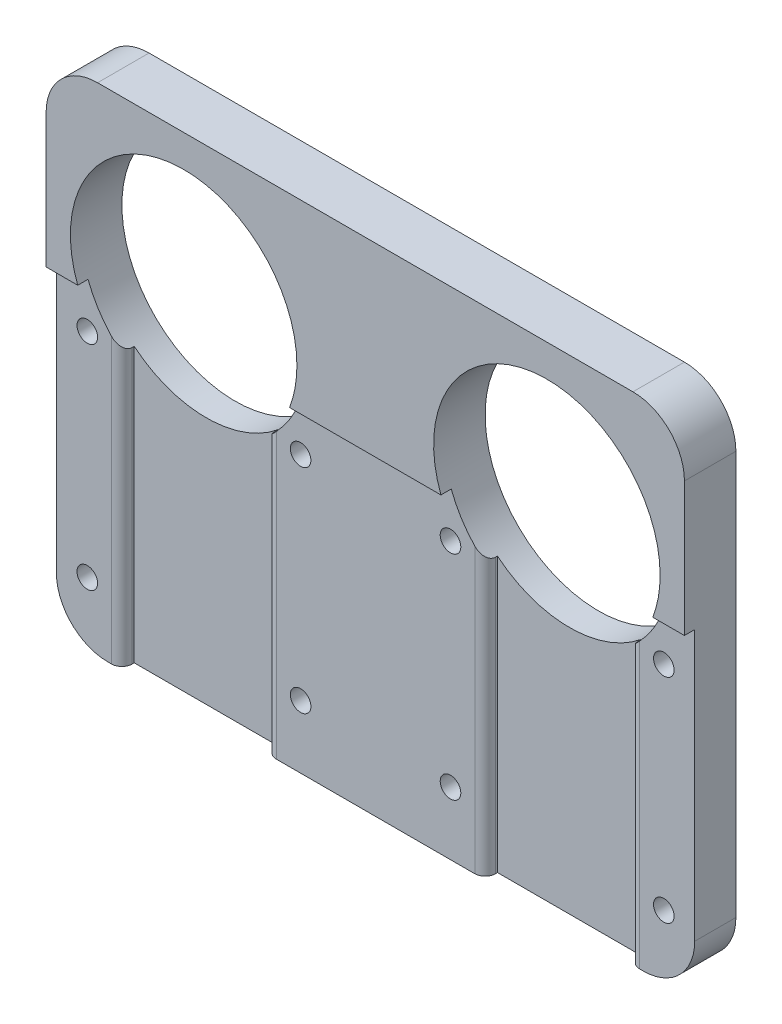
SolidWorks part; units mm, degrees
ref_plane "前视基准面" through (0, 0, 0) normal (0, 0, 1) x (1, 0, 0)
ref_plane "上视基准面" through (0, 0, 0) normal (0, 1, 0) x (1, 0, 0)
ref_plane "右视基准面" through (0, 0, 0) normal (1, 0, 0) x (0, 0, -1)
sketch "草图1" plane through (0, 0, 0) normal (0, 0, 1) x (1, 0, 0)
  line L1 (-5.8171, 42.0726) -> (56.1829, 42.0726)
  line L2 (-5.8171, 42.0726) -> (-5.8171, -3.1474)
  line L3 (-5.8171, -3.1474) -> (56.1829, -3.1474)
  line L4 (56.1829, 42.0726) -> (56.1829, -3.1474)
  dimension "D1" = 45.22
  dimension "D2" = 62
extrude "凸台-拉伸1" add sketch "草图1" along normal blind 4
sketch "草图7" plane through (0, 42.0726, 0) normal (0, 1, 0) x (1, 0, 0)
  line L4 (-5.8171, 0) -> (-5.8171, -4)
  line L5 (56.1829, 0) -> (-5.8171, 0)
  line L6 (-5.8171, 0) -> (-5.8171, -4)
  line L7 (-5.8171, -4) -> (56.1829, -4)
  line L9 (56.1829, 0) -> (-5.8171, 0)
  line L11 (-5.8171, -4) -> (56.1829, -4)
  line L12 (56.1829, -4) -> (56.1829, 0)
  line L13 (56.1829, -4) -> (56.1829, 0)
  dimension "D1" = 0
extrude "凸台-拉伸4" add sketch "草图7" along normal blind 4
sketch "草图2" plane through (0, 0, 4) normal (0, 0, 1) x (1, 0, 0)
  line L0 (-5.8171, 46.0726) -> (-5.8171, -3.1474) construction
  line L1 (-5.8171, -3.1474) -> (56.1829, -3.1474) construction
  line L3 (56.1829, -3.1474) -> (56.1829, 46.0726) construction
  line L5 (0.5429, -3.1474) -> (14.5429, -3.1474)
  line L6 (0.5429, -3.1474) -> (0.5429, 24.8526)
  line L7 (0.5429, 24.8526) -> (14.5429, 24.8526)
  line L8 (14.5429, -3.1474) -> (14.5429, 24.8526)
  line L9 (49.8229, -3.1474) -> (35.8229, -3.1474)
  line L10 (49.8229, -3.1474) -> (49.8229, 24.8526)
  line L11 (49.8229, 24.8526) -> (35.8229, 24.8526)
  line L12 (35.8229, -3.1474) -> (35.8229, 24.8526)
  line L13 (-5.8171, 46.0726) -> (56.1829, 46.0726) construction
  circle A0 centre (-2.8171, 2.9626) radius 1
  circle A1 centre (17.9029, 2.9626) radius 1
  circle A2 centre (-2.8171, 23.6626) radius 1
  circle A3 centre (17.9029, 23.6626) radius 1
  circle A4 centre (7.5429, 31.9626) radius 11
  circle A5 centre (53.1829, 2.9626) radius 1
  circle A6 centre (32.4629, 2.9626) radius 1
  circle A7 centre (32.4629, 23.6626) radius 1
  circle A8 centre (53.1829, 23.6626) radius 1
  circle A9 centre (42.8229, 31.9626) radius 11
  line M9 (-5.8171, -3.1474) -> (56.1829, -3.1474)
  dimension "D1" = 2
  dimension "D2" = 2
  dimension "D3" = 2
  dimension "D4" = 2
  dimension "D5" = 2
  dimension "D6" = 2
  dimension "D7" = 2
  dimension "D8" = 2
  dimension "D9" = 22
  dimension "D10" = 22
  dimension "D11" = 3
  dimension "D12" = 3
  dimension "D13" = 6.11
  dimension "D14" = 6.11
  dimension "D15" = 20.7
  dimension "D17" = 20.7
  dimension "D18" = 20.72
  dimension "D21" = 6.11
  dimension "D22" = 6.11
  dimension "D23" = 3
  dimension "D24" = 20.72
  dimension "D25" = 20.7
  dimension "D26" = 3
  dimension "D27" = 14.11
  dimension "D30" = 20.7
  dimension "D16" = 20.72
  dimension "D19" = 14.11
  dimension "D20" = 13.36
  dimension "D28" = 13.36
  dimension "D29" = 20.72
  dimension "D31" = 28
  dimension "D32" = 14
  dimension "D33" = 6.36
  dimension "D34" = 28
  dimension "D35" = 14
  dimension "D36" = 6.36
extrude "切除-拉伸1" cut sketch "草图2" against normal blind 4 contours L8 A4 L6 L7 | L10 A9 L12 L11 | L6 A4 L8 L7 | L12 A9 L10 L11 | A2 | A3 | A0 | A1 | A7 | A8 | A5 | A6 region at (7.5429, 33.0873, 4) region at (7.5429, 23.2183, 4) region at (42.8229, 23.2183, 4) region at (42.8229, 33.0873, 4)
sketch "草图3" plane through (0, 0, 0) normal (0, 0, -1) x (-1, 0, 0)
  circle A0 centre (-53.1829, 2.9626) radius 2
  circle A1 centre (-32.4629, 2.9626) radius 2
  circle A2 centre (-17.9029, 2.9626) radius 2
  circle A3 centre (2.8171, 2.9626) radius 2
  circle A4 centre (-53.1829, 23.6626) radius 2
  circle A5 centre (-32.4629, 23.6626) radius 2
  circle A6 centre (-17.9029, 23.6626) radius 2
  circle A7 centre (2.8171, 23.6626) radius 2
  dimension "D1" = 4
  dimension "D2" = 4
  dimension "D3" = 4
  dimension "D4" = 4
  dimension "D5" = 4
  dimension "D6" = 4
  dimension "D7" = 4
  dimension "D8" = 4
extrude "切除-拉伸2" cut sketch "草图2<3>" against normal blind 1.2 contours A4 L6 L8 M9 | A9 L12 L10 M9 region at (7.5429, 9.3163, 4) region at (42.8229, 9.3163, 4)
sketch "草图2<3>" plane through (0, 0, 4) normal (0, 0, 1) x (1, 0, 0) same geometry as "草图2"
fillet "圆角2" radius 5 1 edges at (-5.8171, -3.1474, 2)
fillet "圆角4" radius 5 1 edges at (56.1829, -3.1474, 2)
fillet "圆角6" radius 1 1 edges at (14.5429, 10.165, 4)
fillet "圆角7" radius 1 1 edges at (0.5429, 10.165, 4)
fillet "圆角8" radius 1 1 edges at (35.8229, 10.165, 4)
fillet "圆角9" radius 1 1 edges at (49.8229, 10.165, 4)
extrude "切除-拉伸6" cut sketch "草图3" against normal blind 1.5
fillet "圆角10" radius 5 1 edges at (56.1829, 46.0726, 2)
fillet "圆角11" radius 5 1 edges at (-5.8171, 46.0726, 2)
sketch "草图8" plane through (0, 0, 4) normal (0, 0, 1) x (1, 0, 0)
  line L0 (56.1829, 28.0726) -> (-5.8171, 28.0726)
  line L10 (51.1829, 46.0726) -> (-0.8171, 46.0726)
  line L11 (-5.8171, 41.0726) -> (-5.8171, 1.8526)
  line L12 (-0.8171, -3.1474) -> (-0.4571, -3.1474)
  line L13 (-0.4571, -3.1474) -> (-0.4571, 24.4128)
  line L14 (15.5429, 24.4128) -> (15.5429, -3.1474)
  line L15 (15.5429, -3.1474) -> (34.8229, -3.1474)
  line L16 (34.8229, -3.1474) -> (34.8229, 24.4128)
  line L17 (50.8229, 24.4128) -> (50.8229, -3.1474)
  line L18 (50.8229, -3.1474) -> (51.1829, -3.1474)
  line L19 (56.1829, 1.8526) -> (56.1829, 41.0726)
  line L20 (51.1829, 46.0726) -> (-0.8171, 46.0726)
  line L21 (-5.8171, 41.0726) -> (-5.8171, 1.8526)
  line L22 (-0.8171, -3.1474) -> (-0.4571, -3.1474)
  line L23 (-0.4571, -3.1474) -> (-0.4571, 24.4128)
  line L24 (15.5429, 24.4128) -> (15.5429, -3.1474)
  line L25 (15.5429, -3.1474) -> (34.8229, -3.1474)
  line L26 (34.8229, -3.1474) -> (34.8229, 24.4128)
  line L27 (50.8229, 24.4128) -> (50.8229, -3.1474)
  line L28 (50.8229, -3.1474) -> (51.1829, -3.1474)
  line L29 (56.1829, 1.8526) -> (56.1829, 41.0726)
  arc A6 (-0.8171, 46.0726) -> (-5.8171, 41.0726) centre (-0.8171, 41.0726) ccw
  arc A7 (-5.8171, 1.8526) -> (-0.8171, -3.1474) centre (-0.8171, 1.8526) ccw
  arc A8 (15.5429, 24.4128) -> (-0.4571, 24.4128) centre (7.5429, 31.9626) ccw
  arc A9 (50.8229, 24.4128) -> (34.8229, 24.4128) centre (42.8229, 31.9626) ccw
  arc A10 (51.1829, -3.1474) -> (56.1829, 1.8526) centre (51.1829, 1.8526) ccw
  arc A11 (56.1829, 41.0726) -> (51.1829, 46.0726) centre (51.1829, 41.0726) ccw
  arc A12 (-0.8171, 46.0726) -> (-5.8171, 41.0726) centre (-0.8171, 41.0726) ccw
  arc A13 (-5.8171, 1.8526) -> (-0.8171, -3.1474) centre (-0.8171, 1.8526) ccw
  arc A14 (15.5429, 24.4128) -> (-0.4571, 24.4128) centre (7.5429, 31.9626) ccw
  arc A15 (50.8229, 24.4128) -> (34.8229, 24.4128) centre (42.8229, 31.9626) ccw
  arc A16 (51.1829, -3.1474) -> (56.1829, 1.8526) centre (51.1829, 1.8526) ccw
  arc A17 (56.1829, 41.0726) -> (51.1829, 46.0726) centre (51.1829, 41.0726) ccw
  line M26 (51.1829, 46.0726) -> (-0.8171, 46.0726)
  arc M27 (-0.8171, 46.0726) -> (-5.8171, 41.0726) centre (-0.8171, 41.0726) ccw
  line M28 (-5.8171, 41.0726) -> (-5.8171, 1.8526)
  arc M32 (-0.4571, 24.4128) -> (15.5429, 24.4128) centre (7.5429, 31.9626) cw
  arc M36 (34.8229, 24.4128) -> (50.8229, 24.4128) centre (42.8229, 31.9626) cw
  line M40 (56.1829, 1.8526) -> (56.1829, 41.0726)
  arc M41 (56.1829, 41.0726) -> (51.1829, 46.0726) centre (51.1829, 41.0726) ccw
  dimension "D2" = 18
  dimension "D1" = 0
extrude "凸台-拉伸5" add sketch "草图8" along normal blind 1 contours L0 M40 M41 M26 M27 M28 M32 M36 region at (25.1829, 39.335, 4)
